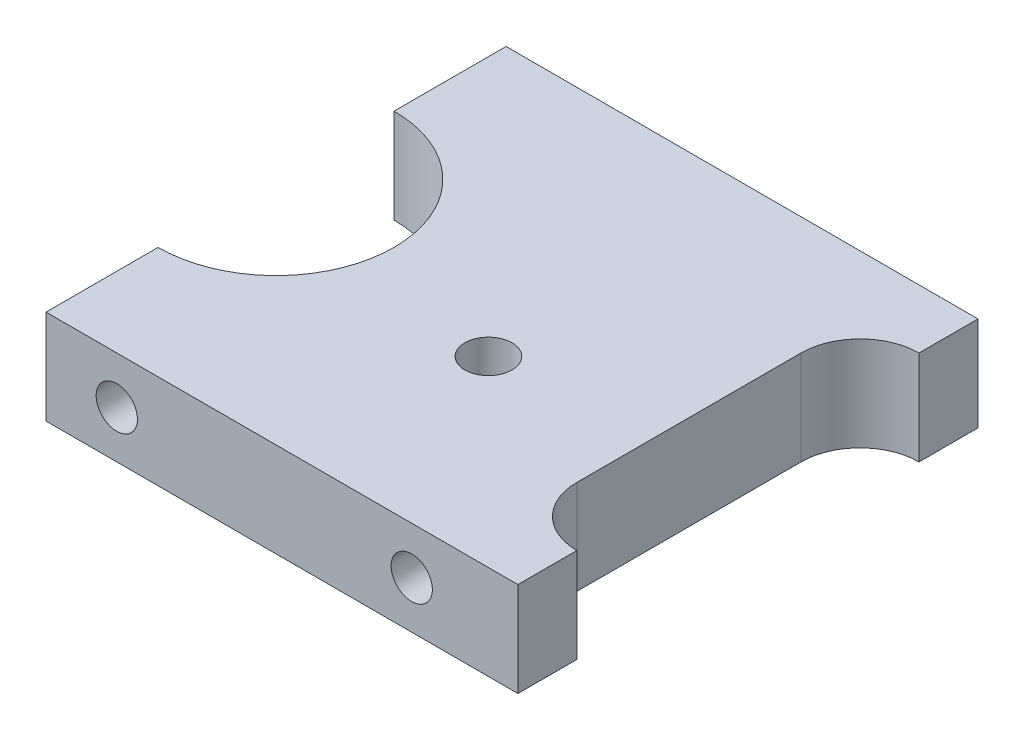
SolidWorks part; units mm, degrees
material "6061 合金"
ref_plane "前视基准面" through (0, 0, 0) normal (0, 0, 1) x (1, 0, 0)
ref_plane "上视基准面" through (0, 0, 0) normal (0, 1, 0) x (1, 0, 0)
ref_plane "右视基准面" through (0, 0, 0) normal (1, 0, 0) x (0, 0, -1)
sketch "草图1" plane through (0, 0, 0) normal (0, 1, 0) x (1, 0, 0)
  line L1 (-22, 23.5) -> (18, 23.5)
  line L2 (-22, 23.5) -> (-22, -15.5)
  line L3 (-22, -15.5) -> (18, -15.5)
  line L4 (18, 23.5) -> (18, -15.5)
  circle A0 centre (0, 0) radius 2
  dimension "D1" = 39
  dimension "D2" = 23.5
  dimension "D3" = 4
  dimension "D4" = 22
  dimension "D5" = 18
extrude "凸台-拉伸1" add sketch "草图1" along normal blind 8
cosmetic thread "装饰螺纹线9" parameters "D2"=5
sketch "草图2" plane through (0, 0, 15.5) normal (0, 0, 1) x (1, 0, 0)
  line L0 (-22, 4) -> (18, 4) construction
  line L1 (-22, 8) -> (-22, 0) construction
  line L2 (18, 8) -> (18, 0) construction
  circle A0 centre (9, 4) radius 1.75
  circle A1 centre (-16, 4) radius 1.75
  dimension "D1" = 25
  dimension "D2" = 34
  dimension "D3" = 3.5
  dimension "D4" = 3.5
extrude "切除-拉伸1" cut sketch "草图2" against normal blind 8
cosmetic thread "装饰螺纹线1" parameters "D1"=8, "D2"=4
cosmetic thread "装饰螺纹线2" parameters "D1"=8, "D2"=4
extrude "切除-拉伸2" cut sketch "草图2<3>" along normal blind 8 from surface starting at face at (-2, 4, -23.5)
sketch "草图2<3>" plane through (0, 0, 15.5) normal (0, 0, 1) x (1, 0, 0) same geometry as "草图2"
cosmetic thread "装饰螺纹线3" parameters "D1"=8, "D2"=4
cosmetic thread "装饰螺纹线4" parameters "D1"=8, "D2"=4
sketch "草图4" plane through (0, 0, 0) normal (0, -1, 0) x (-1, 0, 0)
  line L0 (22, 23.5) -> (22, -15.5) construction
  circle A0 centre (22, 4) radius 10
  dimension "D1" = 20
extrude "切除-拉伸3" cut sketch "草图4" against normal blind 10
sketch "草图6" plane through (0, 8, 0) normal (0, 1, 0) x (1, 0, 0)
  line L0 (18, -5.5) -> (18, 13.5) construction
  line L1 (18, -15.5) -> (18, 23.5) construction
  line L2 (13, -5.5) -> (13, 13.5)
  line L3 (23, -5.5) -> (23, 13.5)
  line L4 (-22, -15.5) -> (18, -15.5) construction
  line L5 (18, 23.5) -> (-22, 23.5) construction
  arc A0 (13, -5.5) -> (23, -5.5) centre (18, -5.5) ccw
  arc A1 (23, 13.5) -> (13, 13.5) centre (18, 13.5) ccw
  point P4 (18, 4)
  dimension "D1" = 5
  dimension "D2" = 10
  dimension "D3" = 10
extrude "切除-拉伸5" cut sketch "草图6" against normal blind 10
